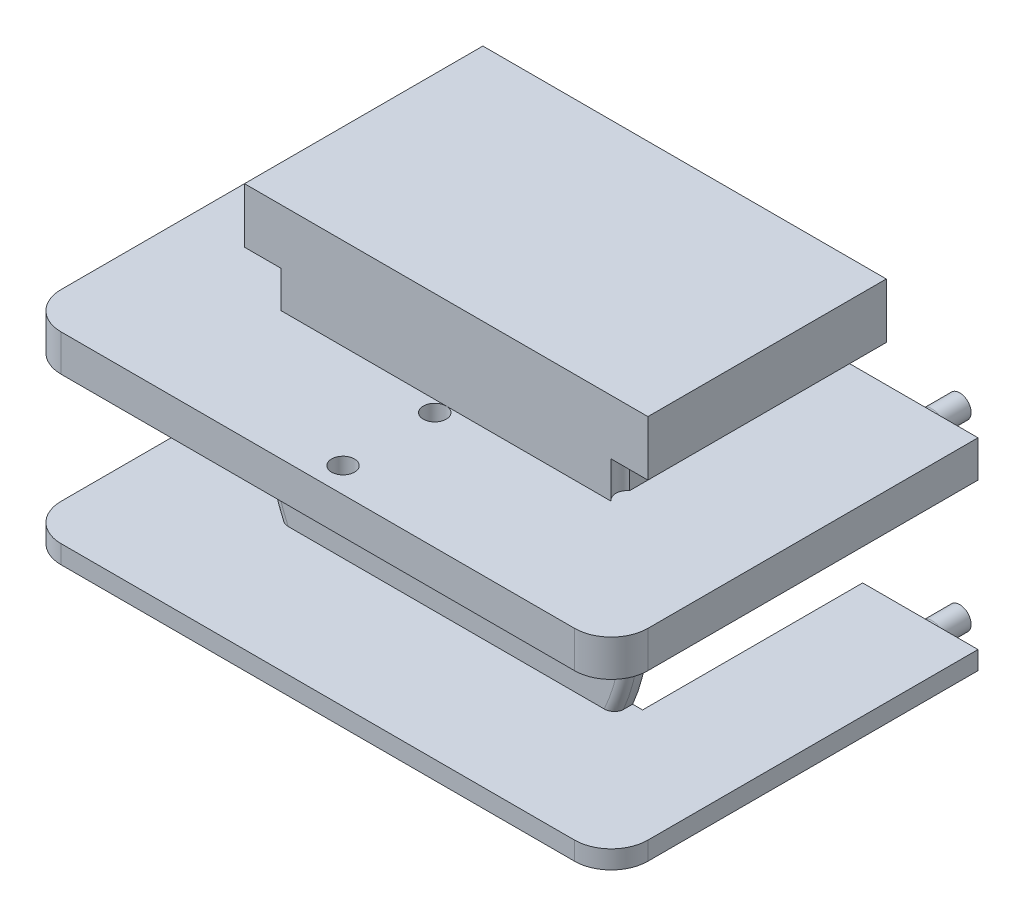
SolidWorks part; units mm, degrees
material "UNOBTANIUM"
ref_plane "Top Plane" through (0, 0, 0) normal (0, 0, 1) x (1, 0, 0)
ref_plane "Right Plane" through (0, 0, 0) normal (0, 1, 0) x (1, 0, 0)
ref_plane "Front Plane" through (0, 0, 0) normal (1, 0, 0) x (0, 0, -1)
ref_axis "x-axis" through (-17.6, 0, 0) along (1, 0, 0)
ref_axis "y-axis" through (0, -9.7375, 0) along (0, 1, 0)
ref_axis "z-axis" through (0, 0, 8.775) along (0, 0, -1)
sketch "Sketch1" plane through (0, 0, 0) normal (0, 0, 1) x (1, 0, 0)
  line L0 (-11, 6) -> (-11, 11)
  line L1 (-11, -6) -> (11, -6)
  line L2 (-11, -6) -> (-11, 6)
  line L3 (-11, 6) -> (11, 6) construction
  line L4 (11, -6) -> (11, 6)
  line L5 (-11, -6) -> (11, 6) construction
  line L6 (-11, 6) -> (11, -6) construction
  line L7 (-11, 11) -> (11, 11)
  line L8 (11, 11) -> (11, 6)
  circle A0 centre (0, 0) radius 9.25 construction
  point P0 (0, 0)
  dimension "D1" = 18.5
  dimension "D2" = 22
  dimension "D3" = 12
  dimension "D4" = 5
extrude "Boss-Extrude1" add sketch "Sketch1" along normal blind 1
sketch "Sketch2" plane through (0, 0, 0) normal (0, 0, -1) x (-1, 0, 0)
  circle A0 centre (0, 0) radius 1.475
  dimension "D1" = 2.95
extrude "Boss-Extrude2" add sketch "Sketch2" along normal blind 14
sketch "Sketch3" plane through (0, 0, 0) normal (0, 0, -1) x (-1, 0, 0)
  line L0 (11, -6) -> (-11, 6) construction
  circle A0 centre (0, 0) radius 1.8
  dimension "D1" = 3.6
extrude "Boss-Extrude3" add sketch "Sketch3" along normal blind 0.75
sketch "Sketch4" plane through (0, 0, 0) normal (0, 0, -1) x (-1, 0, 0)
  line L0 (11, -6) -> (-11, -6) construction
  line L1 (11, 11) -> (9, 11)
  line L2 (11, 11) -> (11, -6)
  line L3 (11, -6) -> (9, -6)
  line L4 (9, 11) -> (9, -6)
  line L5 (0, -6) -> (0, 11) construction
  line L7 (-9, 11) -> (-9, -6)
  line L8 (-11, -6) -> (-9, -6)
  line L9 (-11, 11) -> (-11, -6)
  line L10 (-11, 11) -> (-9, 11)
  line L11 (11, 11) -> (-11, 11) construction
  dimension "D1" = 2
extrude "Boss-Extrude4" add sketch "Sketch4" along normal blind 12
sketch "Sketch5" plane through (0, 0, 0) normal (0, 0, -1) x (-1, 0, 0)
  line L0 (-9, -6) -> (-9, 11) construction
  line L1 (9, 11) -> (-9, 11)
  line L2 (9, 11) -> (9, 9)
  line L3 (9, 9) -> (-9, 9)
  line L4 (-9, 11) -> (-9, 9)
  dimension "D1" = 2
extrude "Boss-Extrude5" add sketch "Sketch5" along normal up to surface (12 mm away) up to face at (-10, 2.5, -12)
sketch "Sketch6" plane through (11, 0, 0) normal (1, 0, 0) x (0, 0, -1)
  line L0 (-1, -6) -> (-1, 11) construction
  line L1 (12, -6) -> (-1, -6)
  line L2 (12, -6) -> (12, -4)
  line L3 (12, -4) -> (-1, -4)
  line L4 (-1, -6) -> (-1, -4)
  line L6 (12, 11) -> (12, -6) construction
  line L7 (-1, 6) -> (12, 6)
  line L8 (-1, 6) -> (-1, 4)
  line L9 (-1, 4) -> (12, 4)
  line L10 (12, 6) -> (12, 4)
  line L11 (5.5, 4) -> (5.5, -4) construction
  line L12 (0, 0) -> (5.5, 0) construction
  line L13 (0, -6) -> (0, 6) construction
  point P21 (5.5, 0)
  dimension "D1" = 2
extrude "Boss-Extrude6" add sketch "Sketch6" along normal blind 5
mirror "Mirror1" about plane through (0, 0, 0) normal (1, 0, 0) of "Boss-Extrude6"
sketch "Sketch7" plane through (0, 0, -12) normal (0, 0, -1) x (-1, 0, 0)
  line L0 (-9, -6) -> (-9, 9) construction
  line L1 (-9, 0) -> (-9, 9)
  line L2 (-9, 9) -> (0, 9)
  line L3 (-9, 0) -> (-9, -6)
  line L4 (-9, -6) -> (-6.7082, -6)
  line L5 (11, -6) -> (-11, -6) construction
  arc A0 (0, 9) -> (-6.7082, -6) centre (0, 0) ccw
  line M18 (-9, -6) -> (-9, 9)
  line M19 (-9, 9) -> (9, 9)
extrude "Boss-Extrude7" add sketch "Sketch7" against normal up to surface (12 mm away) contours A0 L4 M18 | A0 M19 M18 region at (8.3306, -4.5409, -12) region at (6.9897, 6.9897, -12) up to face at (1.8, 0, 0)
sketch "Sketch8" plane through (0, 0, -12) normal (0, 0, -1) x (-1, 0, 0)
  line L0 (-11, 4) -> (-9.1652, 4)
  line L1 (-11, 4) -> (-11, -4)
  line L2 (-11, -4) -> (-9.1652, -4)
  arc A1 (-9.1652, 4) -> (-9.1652, -4) centre (0, 0) ccw
  dimension "D1" = 10
extrude "Cut-Extrude1" cut sketch "Sketch8" against normal through all
sketch "Sketch9" plane through (0, 0, -12) normal (0, 0, -1) x (-1, 0, 0)
  line L0 (-16, -4) -> (-9.1652, -4) construction
  line L1 (-8.0623, 4) -> (-11, 4)
  line L2 (-8.0623, 4) -> (-8.0623, -4)
  line L3 (-8.0623, -4) -> (-11, -4)
  line L4 (-11, 4) -> (-11, -4)
  line L5 (-11, -6) -> (-11, 6) construction
  arc A0 (0, 9) -> (-6.7082, -6) centre (0, 0) ccw construction
  arc A1 (0, 9) -> (-6.7082, -6) centre (0, 0) ccw construction
extrude "Cut-Extrude2" cut sketch "Sketch9" against normal up to surface (12 mm away) up to face at (1.8, 0, 0)
mirror "Mirror2" about plane through (0, 0, 0) normal (1, 0, 0) of "Cut-Extrude2", "Cut-Extrude1", "Boss-Extrude7"
sketch "Sketch21" plane through (0, 0, -12) normal (0, 0, -1) x (-1, 0, 0)
  circle A0 centre (0, 0) radius 10.5
  circle A1 centre (0, 0) radius 9 construction
  circle A2 centre (0, 0) radius 1.8 construction
  circle A3 centre (0, 0) radius 1.8
  dimension "D1" = 1.5
extrude "Cut-Extrude11" cut sketch "Sketch21" against normal up to surface (12 mm away) up to face at (0, -0.7091, 0)
sketch "Sketch10" plane through (0, 0, 1) normal (0, 0, 1) x (1, 0, 0)
  line L0 (-16, -4) -> (-16, -6) construction
  line L1 (16, -6) -> (-16, -6)
  line L2 (16, -6) -> (16, -4)
  line L3 (16, -4) -> (-16, -4)
  line L4 (-16, -6) -> (-16, -4)
  line L5 (-16, -4) -> (-9.1652, -4) construction
  line L7 (-16, 6) -> (16, 6)
  line L8 (-16, 6) -> (-16, 4)
  line L9 (-16, 4) -> (16, 4)
  line L10 (16, 6) -> (16, 4)
extrude "Boss-Extrude8" add sketch "Sketch10" along normal blind 7
fillet "Fillet1" radius 0.5 2 edges at (10, 0, 1) (-10, 0, 1)
sketch "Sketch11" plane through (0, 0, -12) normal (0, 0, -1) x (-1, 0, 0)
  line L0 (-16, -5) -> (-13, -5) construction
  line L1 (-16, -6) -> (-16, -4) construction
  circle A0 centre (-13, -5) radius 0.625
  dimension "D1" = 1.25
  dimension "D2" = 3
extrude "Boss-Extrude9" add sketch "Sketch11" along normal blind 2
sketch "Sketch14" plane through (0, 0, -12) normal (0, 0, -1) x (-1, 0, 0)
  line L1 (11, 6) -> (9, 6)
  line L2 (11, 6) -> (11, 8)
  line L3 (11, 8) -> (9, 8)
  line L4 (9, 6) -> (9, 8)
  line L5 (-11, 6) -> (-9, 6)
  line L6 (-11, 6) -> (-11, 8)
  line L7 (-11, 8) -> (-9, 8)
  line L8 (-9, 6) -> (-9, 8)
  dimension "D1" = 18
  dimension "D2" = 2
extrude "Cut-Extrude5" cut sketch "Sketch14" against normal through all
sketch "Sketch12" plane through (0, 0, -12) normal (0, 0, -1) x (-1, 0, 0)
  line L0 (-16, -5) -> (-13, -5) construction
  line L1 (-16, -6) -> (-16, -4) construction
  line L3 (16, -5) -> (13, -5) construction
  line L4 (16, -6) -> (16, -4) construction
  circle A0 centre (13, -5) radius 0.675
  circle A1 centre (-13, -5) radius 0.625 construction
  circle A2 centre (-13, -5) radius 0.625 construction
  dimension "D1" = 1.35
  dimension "D2" = 1.25
extrude "Cut-Extrude3" cut sketch "Sketch12" against normal blind 2.5
sketch "Sketch16" plane through (0, 6, 0) normal (0, 1, 0) x (1, 0, 0)
  line L0 (-9, -1) -> (-9, 12) construction
  line L1 (-9, 0) -> (-9, -1)
  arc A1 (-9, 0) -> (-9, -1) centre (-9.375, -0.5) cw
  dimension "D1" = 0.25
  dimension "D2" = 1
extrude "Cut-Extrude6" cut sketch "Sketch16" along normal blind 2
mirror "Mirror3" about plane through (0, 0, 0) normal (0, 1, 0) of "Boss-Extrude9", "Cut-Extrude3"
mirror "Mirror4" about plane through (0, 0, 0) normal (1, 0, 0) of "Cut-Extrude6"
fillet "Fillet2" radius 0.5 2 edges at (12.375, 5, -12) (13.625, -5, -12)
fillet "Fillet3" radius 0.5 2 edges at (-13.675, 5, -12) (-13.675, -5, -12)
fillet "Fillet4" radius 2 4 edges at (16, -5, 8) (16, 5, 8) (-16, -5, 8) (-16, 5, 8)
sketch "Sketch17" plane through (0, -6, 0) normal (0, -1, 0) x (1, 0, 0)
  line L0 (-16, 6) -> (-16, -12) construction
  line L1 (-14, 8) -> (14, 8) construction
  line L2 (16, 6) -> (16, -12) construction
  line L3 (-16, 6) -> (-16, -12)
  line L4 (-14, 8) -> (14, 8)
  line L5 (16, 6) -> (16, -12)
  line L6 (14.5, 6) -> (14.5, -12)
  line L8 (-14, 6.5) -> (14, 6.5)
  line L9 (-14.5, 6) -> (-14.5, -12)
  line L10 (14.5, -12) -> (16, -12)
  line L11 (-14.5, -12) -> (-16, -12)
  arc A0 (-14, 8) -> (-16, 6) centre (-14, 6) ccw construction
  arc A1 (16, 6) -> (14, 8) centre (14, 6) ccw construction
  arc A2 (-14, 8) -> (-16, 6) centre (-14, 6) ccw
  arc A3 (16, 6) -> (14, 8) centre (14, 6) ccw
  arc A4 (14.5, 6) -> (14, 6.5) centre (14, 6) ccw
  arc A5 (-14, 6.5) -> (-14.5, 6) centre (-14, 6) ccw
  dimension "D1" = 1.5
extrude "Cut-Extrude7" cut sketch "Sketch17" against normal blind 1 and the other way through all
sketch "Sketch19" plane through (0, 6, 0) normal (0, 1, 0) x (1, 0, 0)
  line L0 (9, -1) -> (-9, -1) construction
  line L1 (0, -1.625) -> (0, -1) construction
  line L2 (9, -1) -> (-9, -1) construction
  circle A0 centre (0, -1.625) radius 0.625
  circle A1 centre (0, -6.625) radius 0.625
  point P4 (0, -1)
  dimension "D1" = 1.25
  dimension "D2" = 5
extrude "Cut-Extrude9" cut sketch "Sketch19" against normal up to surface (2 mm away) up to face at (0.0154, 4, -3.1999)
sketch "Sketch20" plane through (0, 0, -12) normal (0, 0, -1) x (-1, 0, 0)
  line L0 (-9, 8) -> (-11, 8) construction
  line L1 (-11, 11) -> (-9, 11)
  line L2 (-11, 11) -> (-11, 8)
  line L3 (-11, 8) -> (-9, 8)
  line L4 (-9, 11) -> (-9, 8)
  line L5 (11, 11) -> (-11, 11) construction
  line L6 (11, 8) -> (9, 8)
  line L7 (11, 8) -> (11, 11)
  line L8 (11, 11) -> (9, 11)
  line L9 (9, 8) -> (9, 11)
  dimension "D1" = 2
fillet "Fillet5" radius 0.4 1 edges at (-1.475, 0, -14)
equation "\"D1@Sketch12\"=\"D2@Sketch12\"+.1"
